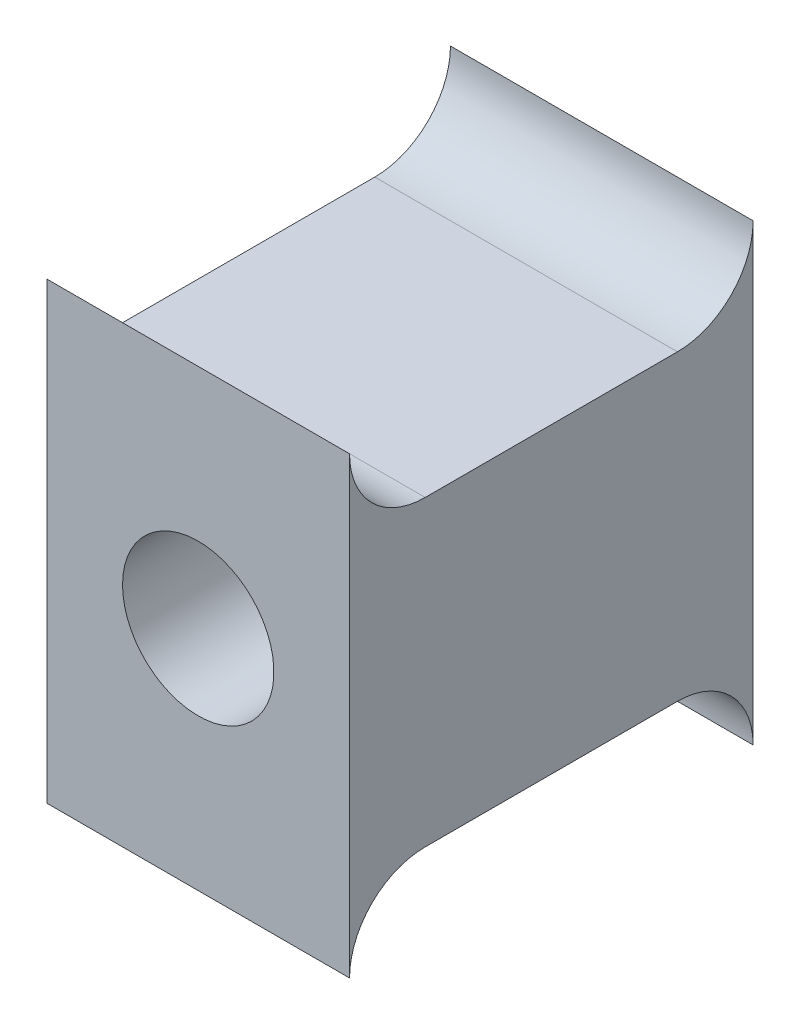
SolidWorks part; units mm, degrees
material "Plain Carbon Steel"
ref_plane "Front Plane" through (0, 0, 0) normal (0, 0, 1) x (1, 0, 0)
ref_plane "Top Plane" through (0, 0, 0) normal (0, 1, 0) x (1, 0, 0)
ref_plane "Right Plane" through (0, 0, 0) normal (1, 0, 0) x (0, 0, -1)
sketch "Sketch1" plane through (0, 0, 0) normal (0, 0, 1) x (1, 0, 0)
  line L0 (-12.7, 0) -> (12.7, 0) construction
  line L1 (12.7, -12.7) -> (-12.7, -12.7)
  line L2 (12.7, -12.7) -> (12.7, 12.7)
  line L3 (12.7, 12.7) -> (-12.7, 12.7)
  line L4 (-12.7, -12.7) -> (-12.7, 12.7)
  line L5 (0, -12.7) -> (0, 12.7) construction
  circle A0 centre (0, 0) radius 6.35
  dimension "D4" = 12.7
  dimension "D1" = 25.4
  dimension "D2" = 25.4
extrude "Boss-Extrude1" add sketch "Sketch1" along normal mid plane 33.8684
sketch "Sketch3" plane through (12.7, 0, 0) normal (1, 0, 0) x (0, 0, -1)
  line L0 (-16.9342, -12.7) -> (-16.9342, 12.7) construction
  line L1 (16.9342, -12.7) -> (16.9342, 12.7) construction
  line L2 (-16.9342, -12.7) -> (-16.9342, 12.7)
  line L3 (16.9342, -12.7) -> (16.9342, 12.7)
  line L4 (0, 0) -> (0, 16.4911) construction
  line L5 (-16.9342, 12.7) -> (-16.9342, 19.05)
  line L6 (-16.9342, 19.05) -> (-21.4893, 19.05)
  line L7 (-21.4893, 19.05) -> (-21.4893, -19.05)
  line L8 (-21.4893, -19.05) -> (-16.9342, -19.05)
  line L9 (-16.9342, -19.05) -> (-16.9342, -12.7)
  line L10 (16.9342, -19.05) -> (16.9342, -12.7)
  line L11 (21.4893, -19.05) -> (16.9342, -19.05)
  line L12 (21.4893, 19.05) -> (21.4893, -19.05)
  line L13 (16.9342, 19.05) -> (21.4893, 19.05)
  line L14 (16.9342, 12.7) -> (16.9342, 19.05)
  dimension "D1" = 38.1
extrude "Boss-Extrude2" add sketch "Sketch3" against normal up to surface (25.4 mm away) up to face at (-12.7, 0, 0)
fillet "Fillet1" radius 6.35 4 edges
extrude "Cut-Extrude1" cut sketch "Sketch3<2>" against normal through all
sketch "Sketch3<2>" plane through (12.7, 0, 0) normal (1, 0, 0) x (0, 0, -1) same geometry as "Sketch3"
